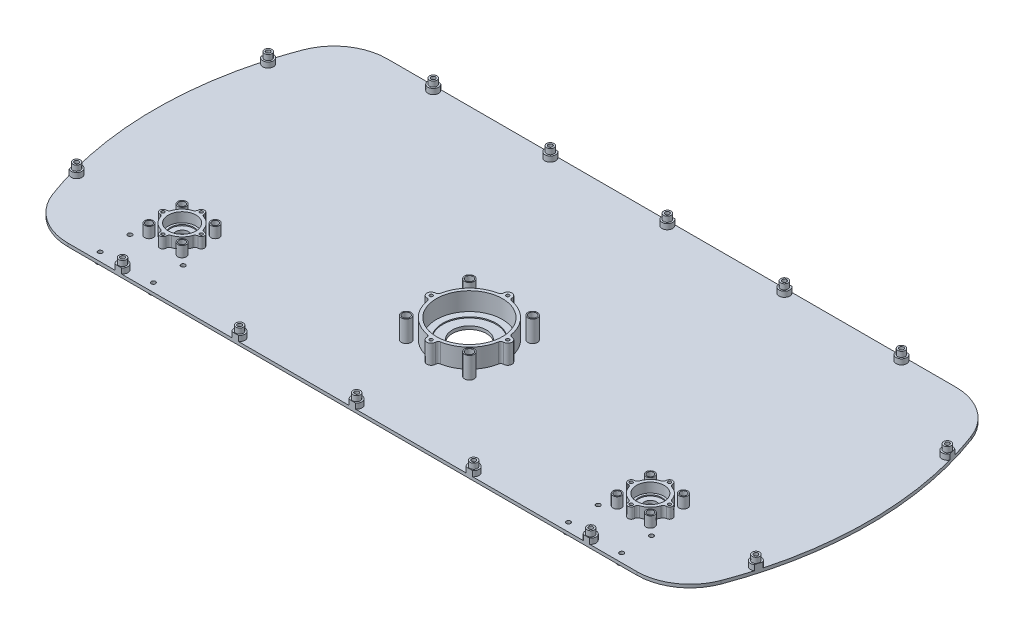
SolidWorks part; units mm, degrees
ref_plane "Front Plane" through (0, 0, 0) normal (0, 0, 1) x (1, 0, 0)
ref_plane "Top Plane" through (0, 0, 0) normal (0, 1, 0) x (1, 0, 0)
ref_plane "Right Plane" through (0, 0, 0) normal (1, 0, 0) x (0, 0, -1)
sketch "Sketch1" plane through (0, 0, 0) normal (0, 1, 0) x (1, 0, 0)
  line L1 (-267.3181, 150) -> (267.3181, 150)
  line L3 (-267.3181, -150) -> (267.3181, -150)
  line L5 (-300, 150) -> (300, -150) construction
  line L6 (-300, -150) -> (300, 150) construction
  arc A0 (314.1486, 117.5186) -> (314.1486, -117.5186) centre (0, 0) cw
  arc A1 (-314.1486, 117.5186) -> (-314.1486, -117.5186) centre (0, 0) ccw
  arc A2 (314.1486, 117.5186) -> (267.3181, 150) centre (267.3181, 100) ccw
  arc A3 (267.3181, -150) -> (314.1486, -117.5186) centre (267.3181, -100) ccw
  arc A4 (-267.3181, -150) -> (-314.1486, -117.5186) centre (-267.3181, -100) cw
  arc A5 (-267.3181, 150) -> (-314.1486, 117.5186) centre (-267.3181, 100) ccw
  circle A6 centre (0, -40) radius 130 construction
  circle A7 centre (-220, -90) radius 60 construction
  circle A8 centre (220, -90) radius 60 construction
  point P0 (0, 0)
  point P19 (0, -40)
  point P26 (300, 150)
  point P27 (300, 150)
  dimension "D3" = 50
  dimension "D5" = 260
  dimension "D6" = 120
  dimension "D7" = 120
  dimension "D1" = 300
  dimension "D2" = 600
  dimension "D4" = 40
  dimension "D8" = 90
  dimension "D9" = 220
  dimension "D10" = 90
  dimension "D11" = 220
extrude "Boss-Extrude1" add sketch "Sketch1" along normal blind 3
sketch "Sketch2" plane through (0, 3, 0) normal (0, 1, 0) x (1, 0, 0)
  circle A0 centre (220, -90) radius 60 construction
  circle A1 centre (-220, -90) radius 60 construction
  circle A2 centre (220, -90) radius 60 construction
  circle A3 centre (-220, -90) radius 60 construction
  circle A4 centre (-220, -90) radius 6
  circle A5 centre (220, -90) radius 6
  circle A6 centre (0, -40) radius 17.5
  circle A7 centre (220, -90) radius 11
  circle A8 centre (220, -90) radius 13
  circle A9 centre (-220, -90) radius 13
  circle A10 centre (-220, -90) radius 11
  circle A13 centre (-220, -90) radius 16
  circle A14 centre (220, -90) radius 16
  circle A15 centre (238, -90) radius 1.5
  arc A16 (235.8611, -87.8964) -> (235.8611, -92.1036) centre (238, -90) cw
  arc A17 (222.1036, -105.8611) -> (217.8964, -105.8611) centre (220, -108) cw
  circle A18 centre (220, -108) radius 1.5
  arc A19 (204.1389, -92.1036) -> (204.1389, -87.8964) centre (202, -90) cw
  circle A20 centre (202, -90) radius 1.5
  arc A21 (217.8964, -74.1389) -> (222.1036, -74.1389) centre (220, -72) cw
  circle A22 centre (220, -72) radius 1.5
  arc A23 (202, -87) -> (204.8114, -84.9696) centre (202, -84.0385) ccw
  arc A24 (202, -93) -> (204.8114, -95.0304) centre (202, -95.9615) cw
  arc A25 (223, -72) -> (225.0304, -74.8114) centre (225.9615, -72) ccw
  arc A26 (217, -72) -> (214.9696, -74.8114) centre (214.0385, -72) cw
  arc A27 (238, -93) -> (235.1886, -95.0304) centre (238, -95.9615) ccw
  arc A28 (238, -87) -> (235.1886, -84.9696) centre (238, -84.0385) cw
  arc A29 (217, -108) -> (214.9696, -105.1886) centre (214.0385, -108) ccw
  arc A30 (223, -108) -> (225.0304, -105.1886) centre (225.9615, -108) cw
  point P36 (220, -90)
  point P61 (220, -90)
  dimension "D1" = 35
  dimension "D2" = 26
  dimension "D3" = 22
  dimension "D4" = 26
  dimension "D5" = 22
  dimension "D6" = 12
  dimension "D7" = 12
  dimension "D8" = 3
  dimension "D9" = 3
  dimension "D10" = 3
  dimension "D11" = 18
  dimension "D12" = 4
  dimension "D13" = 4
extrude "Cut-Extrude1" cut sketch "Sketch2" against normal blind 10 contours A4 | A5 region at (-220, 3, 90) region at (220, 3, 90)
extrude "Boss-Extrude2" add sketch "Sketch2<3>" along normal blind 1 from surface contours A9 A10 | A8 A7 region at (207.3677, 3, 90) region at (-232.6323, 3, 90) starting at face at (-220, 3, 96)
sketch "Sketch2<3>" plane through (0, 3, 0) normal (0, 1, 0) x (1, 0, 0) same geometry as "Sketch2"
extrude "Boss-Extrude3" add sketch "Sketch2<4>" along normal blind 10 from surface contours A14 A8 | A19 A14 A20 | A21 A14 A22 | A16 A14 A15 | A17 A14 A18 | A23 A19 A14 | A19 A24 A14 | A25 A21 A14 | A21 A26 A14 | A16 A28 A14 | A27 A16 A14 | A17 A30 A14 | A29 A17 A14 region at (235.5137, 3, 91.0243) region at (236.0441, 3, 88.9407) region at (236.2045, 3, 86.846) region at (236.2045, 3, 93.154) region at (223.154, 3, 73.7955) region at (223.154, 3, 106.2045) region at (220, 3, 73.921) region at (222.694, 3, 106.871) region at (216.846, 3, 73.7955) region at (216.846, 3, 106.2045) region at (203.7955, 3, 86.846) region at (203.7955, 3, 93.154) region at (203.921, 3, 90) starting at face at (220, 3, 103)
sketch "Sketch2<4>" plane through (0, 3, 0) normal (0, 1, 0) x (1, 0, 0) same geometry as "Sketch2"
sketch "Sketch3" plane through (0, 3, 0) normal (0, 1, 0) x (1, 0, 0)
  circle A0 centre (0, -40) radius 16
  circle A1 centre (0, -40) radius 25
  circle A2 centre (0, -40) radius 31
  circle A3 centre (0, -40) radius 34
  circle A4 centre (36, -40) radius 1.5
  arc A6 (33.8333, -43.3624) -> (33.8333, -36.6376) centre (36, -40) ccw
  arc A7 (-3.3624, -73.8333) -> (3.3624, -73.8333) centre (0, -76) ccw
  circle A8 centre (0, -76) radius 1.5
  arc A9 (-33.8333, -36.6376) -> (-33.8333, -43.3624) centre (-36, -40) ccw
  circle A10 centre (-36, -40) radius 1.5
  arc A11 (3.3624, -6.1667) -> (-3.3624, -6.1667) centre (0, -4) ccw
  circle A12 centre (0, -4) radius 1.5
  arc A13 (-36, -36) -> (-33.4426, -33.8689) centre (-36, -33.4) ccw
  arc A14 (-36, -44) -> (-33.4426, -46.1311) centre (-36, -46.6) cw
  arc A15 (4, -4) -> (6.1311, -6.5574) centre (6.6, -4) ccw
  arc A16 (-4, -4) -> (-6.1311, -6.5574) centre (-6.6, -4) cw
  arc A17 (36, -44) -> (33.4426, -46.1311) centre (36, -46.6) ccw
  arc A18 (36, -36) -> (33.4426, -33.8689) centre (36, -33.4) cw
  arc A19 (-4, -76) -> (-6.1311, -73.4426) centre (-6.6, -76) ccw
  arc A20 (4, -76) -> (6.1311, -73.4426) centre (6.6, -76) cw
  point P25 (0, -40)
  point P50 (0, -40)
  dimension "D1" = 32
  dimension "D2" = 62
  dimension "D3" = 3
  dimension "D4" = 50
  dimension "D5" = 4
  dimension "D7" = 3
  dimension "D6" = 36
  dimension "D8" = 4
  dimension "D9" = 4
extrude "Cut-Extrude8" cut sketch "Sketch3" against normal blind 10 contours A0 region at (0, 3, 40)
extrude "Boss-Extrude4" add sketch "Sketch3<3>" along normal blind 1 from surface contours A2 A1 region at (-30.1232, 3, 40) starting at face at (0, 3, 56)
sketch "Sketch3<3>" plane through (0, 3, 0) normal (0, 1, 0) x (1, 0, 0) same geometry as "Sketch3"
extrude "Boss-Extrude5" add sketch "Sketch3<4>" along normal blind 18 from surface contours A3 A2 | A3 A6 A4 | A3 A7 A8 | A3 A9 A10 | A3 A11 A12 | A13 A9 A3 | A9 A14 A3 | A11 A16 A3 | A15 A11 A3 | A17 A6 A3 | A6 A18 A3 | A7 A20 A3 | A19 A7 A3 region at (32.9978, 3, 41.6356) region at (34.0592, 3, 38.3117) region at (34.2416, 3, 35.7431) region at (34.2416, 3, 44.2569) region at (4.2569, 3, 5.7584) region at (4.2569, 3, 74.2416) region at (0, 3, 5.899) region at (3.7404, 3, 74.8992) region at (-4.2569, 3, 5.7584) region at (-4.2569, 3, 74.2416) region at (-34.2416, 3, 35.7431) region at (-34.2416, 3, 44.2569) region at (-34.101, 3, 40) starting at face at (0, 3, 71)
sketch "Sketch3<4>" plane through (0, 3, 0) normal (0, 1, 0) x (1, 0, 0) same geometry as "Sketch3"
mirror "Mirror1" about plane through (0, 0, 0) normal (1, 0, 0) of "Boss-Extrude3"
sketch "Sketch4" plane through (0, 3, 0) normal (0, 1, 0) x (1, 0, 0)
  line B0 (0, -40) -> (-78.0469, 38.0469) construction
  circle B1 centre (-29.6985, -10.3015) radius 2
  circle B2 centre (-29.6985, -10.3015) radius 4.5
  circle B3 centre (-29.6985, -10.3015) radius 3.5
  circle B4 centre (29.6985, -10.3015) radius 4.5
  circle B5 centre (29.6985, -10.3015) radius 3.5
  circle B6 centre (29.6985, -10.3015) radius 2
  circle B7 centre (29.6985, -69.6985) radius 4.5
  circle B8 centre (29.6985, -69.6985) radius 3.5
  circle B9 centre (29.6985, -69.6985) radius 2
  circle B10 centre (-29.6985, -69.6985) radius 4.5
  circle B11 centre (-29.6985, -69.6985) radius 3.5
  circle B12 centre (-29.6985, -69.6985) radius 2
  circle B13 centre (-29.6985, -10.3015) radius 6.5
  arc B14 (-31.7007, -27.4352) -> (-34.2947, -14.8977) centre (-42.5371, -23.1401) ccw
  arc B15 (-12.5648, -8.2993) -> (-25.1023, -5.7053) centre (-16.8599, 2.5371) cw
  arc B16 (12.5648, -8.2993) -> (25.1023, -5.7053) centre (16.8599, 2.5371) ccw
  arc B17 (31.7007, -27.4352) -> (34.2947, -14.8977) centre (42.5371, -23.1401) cw
  circle B18 centre (29.6985, -10.3015) radius 6.5
  arc B19 (31.7007, -52.5648) -> (34.2947, -65.1023) centre (42.5371, -56.8599) ccw
  arc B20 (12.5648, -71.7007) -> (25.1023, -74.2947) centre (16.8599, -82.5371) cw
  circle B21 centre (29.6985, -69.6985) radius 6.5
  arc B22 (-12.5648, -71.7007) -> (-25.1023, -74.2947) centre (-16.8599, -82.5371) ccw
  arc B23 (-31.7007, -52.5648) -> (-34.2947, -65.1023) centre (-42.5371, -56.8599) cw
  circle B24 centre (-29.6985, -69.6985) radius 6.5
  circle B25 centre (0, -40) radius 34.1
  circle B26 centre (3.6047, -60.6883) radius 2.7
  circle B27 centre (-19.7189, -32.7776) radius 2.7
  circle B28 centre (16.1143, -26.5341) radius 2.7
  circle B29 centre (0, -40) radius 6.5
sketch_block_instance "Block2-1"
sketch_block "Block2" parameters "D1"=4, "D2"=7, "D3"=9, "D4"=13
sketch_block_instance "Block1-1"
sketch_block "Block1"
extrude "Boss-Extrude6" add sketch "Sketch4" along normal blind 20 contours B4 B5 | B5 B6 | B2 B3 | B3 B1 | B7 B8 | B8 B9 | B10 B11 | B11 B12 region at (-34.0712, 3, 10.3015) region at (-33.0995, 3, 10.3015) region at (25.3258, 3, 10.3015) region at (26.2975, 3, 10.3015) region at (25.3258, 3, 69.6985) region at (26.2975, 3, 69.6985) region at (-34.0712, 3, 69.6985) region at (-33.0995, 3, 69.6985)
extrude "Cut-Extrude9" cut sketch "Sketch4<3>" against normal blind 5 from surface contours B3 B1 | B5 B6 | B8 B9 | B11 B12 region at (-33.0995, 3, 10.3015) region at (26.2975, 3, 10.3015) region at (26.2975, 3, 69.6985) region at (-33.0995, 3, 69.6985) starting at face at (-29.6985, 23, 14.8015)
sketch "Sketch4<3>" plane through (0, 3, 0) normal (0, 1, 0) x (1, 0, 0) same geometry as "Sketch4"
sketch "Sketch5" plane through (0, 3, 0) normal (0, 1, 0) x (1, 0, 0)
  circle B0 centre (204.4437, -74.4437) radius 1.5
  circle B1 centre (204.4437, -74.4437) radius 3
  circle B2 centre (204.4437, -74.4437) radius 4
  circle B3 centre (204.4437, -105.5563) radius 1.5
  arc B4 (200.5546, -101.6673) -> (208.3327, -109.4454) centre (204.4437, -105.5563) ccw
  arc B5 (218.4477, -105.824) -> (208.3327, -109.4454) centre (217.2205, -118.3332) ccw
  arc B6 (218.4477, -105.824) -> (221.5523, -105.824) centre (220, -90) ccw
  arc B7 (231.6673, -109.4454) -> (221.5523, -105.824) centre (222.7795, -118.3332) ccw
  arc B8 (231.6673, -109.4454) -> (239.4454, -101.6673) centre (235.5563, -105.5563) ccw
  arc B9 (235.824, -91.5523) -> (239.4454, -101.6673) centre (248.3332, -92.7795) ccw
  arc B10 (235.824, -91.5523) -> (235.824, -88.4477) centre (220, -90) ccw
  arc B11 (239.4454, -78.3327) -> (235.824, -88.4477) centre (248.3332, -87.2205) ccw
  arc B12 (239.4454, -78.3327) -> (231.6673, -70.5546) centre (235.5563, -74.4437) ccw
  arc B13 (221.5523, -74.176) -> (231.6673, -70.5546) centre (222.7795, -61.6668) ccw
  arc B14 (221.5523, -74.176) -> (218.4477, -74.176) centre (220, -90) ccw
  arc B15 (208.3327, -70.5546) -> (218.4477, -74.176) centre (217.2205, -61.6668) ccw
  arc B16 (208.3327, -70.5546) -> (200.5546, -78.3327) centre (204.4437, -74.4437) ccw
  arc B17 (204.176, -88.4477) -> (200.5546, -78.3327) centre (191.6668, -87.2205) ccw
  arc B18 (204.176, -88.4477) -> (204.176, -91.5523) centre (220, -90) ccw
  arc B19 (200.5546, -101.6673) -> (204.176, -91.5523) centre (191.6668, -92.7795) ccw
  circle B20 centre (204.4437, -105.5563) radius 3
  circle B21 centre (204.4437, -105.5563) radius 4
  circle B22 centre (235.5563, -105.5563) radius 1.5
  circle B23 centre (235.5563, -105.5563) radius 3
  circle B24 centre (235.5563, -105.5563) radius 4
  circle B25 centre (235.5563, -74.4437) radius 1.5
  circle B26 centre (235.5563, -74.4437) radius 3
  circle B27 centre (235.5563, -74.4437) radius 4
sketch_block_instance "Block3-1"
sketch_block "Block3"
extrude "Boss-Extrude7" add sketch "Sketch5" along normal blind 10 contours B27 B26 | B26 B25 | B2 B1 | B1 B0 | B24 B23 | B23 B22 | B20 B3 | B21 B20 region at (201.5285, 3, 74.4437) region at (200.5568, 3, 74.4437) region at (201.5285, 3, 105.5563) region at (200.5568, 3, 105.5563) region at (232.6412, 3, 105.5563) region at (231.6695, 3, 105.5563) region at (232.6412, 3, 74.4437) region at (231.6695, 3, 74.4437)
extrude "Cut-Extrude10" cut sketch "Sketch5<3>" against normal blind 5 from surface contours B20 B3 | B1 B0 | B26 B25 | B23 B22 region at (201.5285, 3, 74.4437) region at (201.5285, 3, 105.5563) region at (232.6412, 3, 105.5563) region at (232.6412, 3, 74.4437) starting at face at (235.5563, 13, 109.5563)
sketch "Sketch5<3>" plane through (0, 3, 0) normal (0, 1, 0) x (1, 0, 0) same geometry as "Sketch5"
mirror "Mirror2" about plane through (0, 0, 0) normal (1, 0, 0) of "Boss-Extrude7", "Cut-Extrude10"
sketch "Sketch7" plane through (0, 0, 0) normal (0, -1, 0) x (1, 0, 0)
  line B0 (220, 61) -> (-220, 61)
  line B1 (220, 119) -> (-220, 119)
  line B2 (220, 121) -> (-220, 121)
  line B3 (220, 59) -> (-220, 59)
  arc B4 (220, 119) -> (220, 61) centre (220, 90) cw
  arc B5 (-220, 119) -> (-220, 61) centre (-220, 90) ccw
  arc B6 (-220, 121) -> (-220, 59) centre (-220, 90) ccw
  arc B7 (220, 121) -> (220, 59) centre (220, 90) cw
  circle B8 centre (0, 115.25) radius 2
  circle B9 centre (0, 64.75) radius 2
  arc B10 (-3.3072, 119) -> (3.3072, 119) centre (0, 115.25) ccw
  arc B11 (-3.3072, 61) -> (3.3072, 61) centre (0, 64.75) cw
  circle B12 centre (0, 115.25) radius 3.5
  circle B13 centre (0, 64.75) radius 3.5
sketch_block_instance "Block5-1"
sketch_block "Block5" parameters "D4"=4, "D7"=4, "D1"=440, "D2"=29, "D3"=29, "D5"=7, "D6"=3, "D8"=8.5, "D9"=3.75, "D10"=8.5, "D11"=3.75, "D12"=2
sketch "Sketch8" plane through (0, 0, 0) normal (0, -1, 0) x (1, 0, 0)
  line L0 (-267.3181, 150) -> (267.3181, 150) construction
  circle B0 centre (-245, 114) radius 4.525
  circle B1 centre (-245, 142) radius 4.525
  circle B2 centre (-195, 142) radius 3.525
  circle B3 centre (-195, 142) radius 2
  circle B4 centre (-195, 142) radius 4.525
  circle B5 centre (-195, 114) radius 4.525
  circle B6 centre (-195, 114) radius 3.525
  circle B7 centre (-195, 114) radius 2
  circle B8 centre (-245, 114) radius 2
  circle B9 centre (-245, 114) radius 3.525
  circle B10 centre (-245, 142) radius 2
  circle B11 centre (-245, 142) radius 3.525
  dimension "D1" = 8
sketch_block_instance "Block7-1"
sketch_block "Block7" parameters "D1"=25, "D2"=14
sketch_block_instance "Block6-1"
sketch_block "Block6"
extrude "Boss-Extrude8" add sketch "Sketch8" along normal blind 5 contours B11 B10 | B2 B3 | B6 B7 | B9 B8 region at (-198.4253, 0, 142) region at (-198.4253, 0, 114) region at (-248.4253, 0, 114) region at (-248.4253, 0, 142)
extrude "Cut-Extrude11" cut sketch "Sketch8<3>" against normal blind 10 contours B3 | B7 | B8 | B10 region at (-195, 0, 142) region at (-195, 0, 114) region at (-245, 0, 114) region at (-245, 0, 142)
sketch "Sketch8<3>" plane through (0, 0, 0) normal (0, -1, 0) x (1, 0, 0) same geometry as "Sketch8"
mirror "Mirror3" about plane through (0, 0, 0) normal (1, 0, 0) of "Cut-Extrude11", "Boss-Extrude8"
sketch "Sketch9" plane through (0, 0, 0) normal (0, -1, 0) x (1, 0, 0)
  line L0 (-267.3181, 150) -> (267.3181, 150) construction
  line L1 (-267.3181, -150) -> (267.3181, -150) construction
  line L2 (-267.3181, 150) -> (267.3181, 150)
  line L3 (-267.3181, -150) -> (267.3181, -150)
  arc A0 (314.1486, 117.5186) -> (267.3181, 150) centre (267.3181, 100) ccw construction
  arc A1 (314.1486, -117.5186) -> (314.1486, 117.5186) centre (0, 0) ccw construction
  arc A2 (267.3181, -150) -> (314.1486, -117.5186) centre (267.3181, -100) ccw construction
  arc A3 (-314.1486, -117.5186) -> (-267.3181, -150) centre (-267.3181, -100) ccw construction
  arc A4 (-314.1486, 117.5186) -> (-314.1486, -117.5186) centre (0, 0) ccw construction
  arc A5 (-267.3181, 150) -> (-314.1486, 117.5186) centre (-267.3181, 100) ccw construction
  arc A6 (314.1486, 117.5186) -> (267.3181, 150) centre (267.3181, 100) ccw
  arc A7 (314.1486, -117.5186) -> (314.1486, 117.5186) centre (0, 0) ccw
  arc A8 (267.3181, -150) -> (314.1486, -117.5186) centre (267.3181, -100) ccw
  arc A9 (-314.1486, -117.5186) -> (-267.3181, -150) centre (-267.3181, -100) ccw
  arc A10 (-314.1486, 117.5186) -> (-314.1486, -117.5186) centre (0, 0) ccw
  arc A11 (-267.3181, 150) -> (-314.1486, 117.5186) centre (-267.3181, 100) ccw
  circle A12 centre (0, -146) radius 2
  circle A13 centre (0, -146) radius 3.5
  circle A14 centre (0, -146) radius 5
  circle A15 centre (319.1486, -90) radius 2
  circle A16 centre (319.1486, -90) radius 3.5
  circle A17 centre (319.1486, -90) radius 5
  point P20 (312.3808, -90)
  point P21 (287.3212, -90)
  point P25 (338.4041, -90)
  dimension "D1" = 4
  dimension "D2" = 1.5
  dimension "D3" = 1.5
  dimension "D5" = 4
  dimension "D6" = 1.5
  dimension "D7" = 1.5
  dimension "D9" = 5
  dimension "D4" = 4
  dimension "D8" = 60
extrude "Cut-Extrude12" cut sketch "Sketch9" against normal blind 10 contours A12 region at (0, 0, -146)
extrude "Boss-Extrude9" add sketch "Sketch9<3>" against normal blind 10 from surface contours A13 A12 region at (-3.401, 0, -146) starting at face at (0, 3, -144)
sketch "Sketch9<3>" plane through (0, 0, 0) normal (0, -1, 0) x (1, 0, 0) same geometry as "Sketch9"
pattern_linear "LPattern1" count 3 spacing 110 along (1, 0, 0) of "Cut-Extrude12", "Boss-Extrude9"
pattern_linear "LPattern2" count 3 spacing 110 along (-1, 0, 0) of "Cut-Extrude12", "Boss-Extrude9"
mirror "Mirror4" about plane through (0, 0, 0) normal (0, 0, 1) of "LPattern2", "LPattern1"
extrude "Cut-Extrude13" cut sketch "Sketch9<5>" against normal blind 10 contours A15 region at (319.1486, 0, -90)
sketch "Sketch9<5>" plane through (0, 0, 0) normal (0, -1, 0) x (1, 0, 0) same geometry as "Sketch9"
extrude "Boss-Extrude10" add sketch "Sketch9<6>" against normal blind 10 from surface contours A16 A15 region at (315.7476, 0, -90) starting at face at (319.1486, 3, -88)
sketch "Sketch9<6>" plane through (0, 0, 0) normal (0, -1, 0) x (1, 0, 0) same geometry as "Sketch9"
mirror "Mirror9" about plane through (0, 0, 0) normal (0, 0, 1) of "Boss-Extrude10", "Cut-Extrude13" second plane through (0, 0, 0) second plane normal (1, 0, 0)
extrude "Boss-Extrude11" add sketch "Sketch9<7>" against normal blind 5 from surface contours L3 A14 A13 region at (-2.1759, 0, -141.6482) starting at face at (-319.1486, 3, 86.5)
sketch "Sketch9<7>" plane through (0, 0, 0) normal (0, -1, 0) x (1, 0, 0) same geometry as "Sketch9"
pattern_linear "LPattern3" count 3 spacing 110 along (1, 0, 0) of "Boss-Extrude11"
pattern_linear "LPattern4" count 3 spacing 110 along (-1, 0, 0) of "LPattern3"
mirror "Mirror10" about plane through (0, 0, 0) normal (0, 0, 1) of "Boss-Extrude11", "LPattern3", "LPattern4"
extrude "Boss-Extrude12" add sketch "Sketch9<8>" against normal blind 5 from surface contours A7 A17 A16 region at (322.6867, 0, -90.9977) starting at face at (-319.1486, 3, 86.5)
sketch "Sketch9<8>" plane through (0, 0, 0) normal (0, -1, 0) x (1, 0, 0) same geometry as "Sketch9"
mirror "Mirror18" about plane through (0, 0, 0) normal (1, 0, 0) of "Boss-Extrude12"
mirror "Mirror19" about plane through (0, 0, 0) normal (0, 0, 1) of "Mirror18"
sketch "Sketch10" plane through (0, 3, 0) normal (0, 1, 0) x (1, 0, 0)
  line L0 (-267.3181, 150) -> (267.3181, 150) construction
  line L1 (-267.3181, -150) -> (267.3181, -150) construction
  line L2 (-267.3181, 150) -> (267.3181, 150)
  line L3 (-267.3181, -150) -> (267.3181, -150)
  circle A0 centre (-220, -146) radius 2 construction
  circle A1 centre (-220, -146) radius 3.5 construction
  arc A2 (-217, -150) -> (-223, -150) centre (-220, -146) ccw construction
  circle A3 centre (-319.1486, 90) radius 2 construction
  circle A4 centre (-319.1486, 90) radius 3.5 construction
  arc A5 (-323.687, 87.9017) -> (-321.9221, 94.1603) centre (-319.1486, 90) ccw construction
  circle A6 centre (-220, 146) radius 2 construction
  circle A7 centre (-220, 146) radius 3.5 construction
  arc A8 (-223, 150) -> (-217, 150) centre (-220, 146) ccw construction
  arc A9 (314.1486, 117.5186) -> (267.3181, 150) centre (267.3181, 100) ccw construction
  arc A10 (314.1486, -117.5186) -> (314.1486, 117.5186) centre (0, 0) ccw construction
  arc A11 (267.3181, -150) -> (314.1486, -117.5186) centre (267.3181, -100) ccw construction
  arc A12 (-314.1486, -117.5186) -> (-267.3181, -150) centre (-267.3181, -100) ccw construction
  arc A13 (-314.1486, 117.5186) -> (-314.1486, -117.5186) centre (0, 0) ccw construction
  arc A14 (-267.3181, 150) -> (-314.1486, 117.5186) centre (-267.3181, 100) ccw construction
  circle A15 centre (-220, -146) radius 2
  circle A16 centre (-220, -146) radius 3.5
  arc A17 (-217, -150) -> (-223, -150) centre (-220, -146) ccw
  circle A18 centre (-319.1486, 90) radius 2
  circle A19 centre (-319.1486, 90) radius 3.5
  arc A20 (-323.687, 87.9017) -> (-321.9221, 94.1603) centre (-319.1486, 90) ccw
  circle A21 centre (-220, 146) radius 2
  circle A22 centre (-220, 146) radius 3.5
  arc A23 (-223, 150) -> (-217, 150) centre (-220, 146) ccw
  arc A24 (314.1486, 117.5186) -> (267.3181, 150) centre (267.3181, 100) ccw
  arc A25 (314.1486, -117.5186) -> (314.1486, 117.5186) centre (0, 0) ccw
  arc A26 (267.3181, -150) -> (314.1486, -117.5186) centre (267.3181, -100) ccw
  arc A27 (-314.1486, -117.5186) -> (-267.3181, -150) centre (-267.3181, -100) ccw
  arc A28 (-314.1486, 117.5186) -> (-314.1486, -117.5186) centre (0, 0) ccw
  arc A29 (-267.3181, 150) -> (-314.1486, 117.5186) centre (-267.3181, 100) ccw
